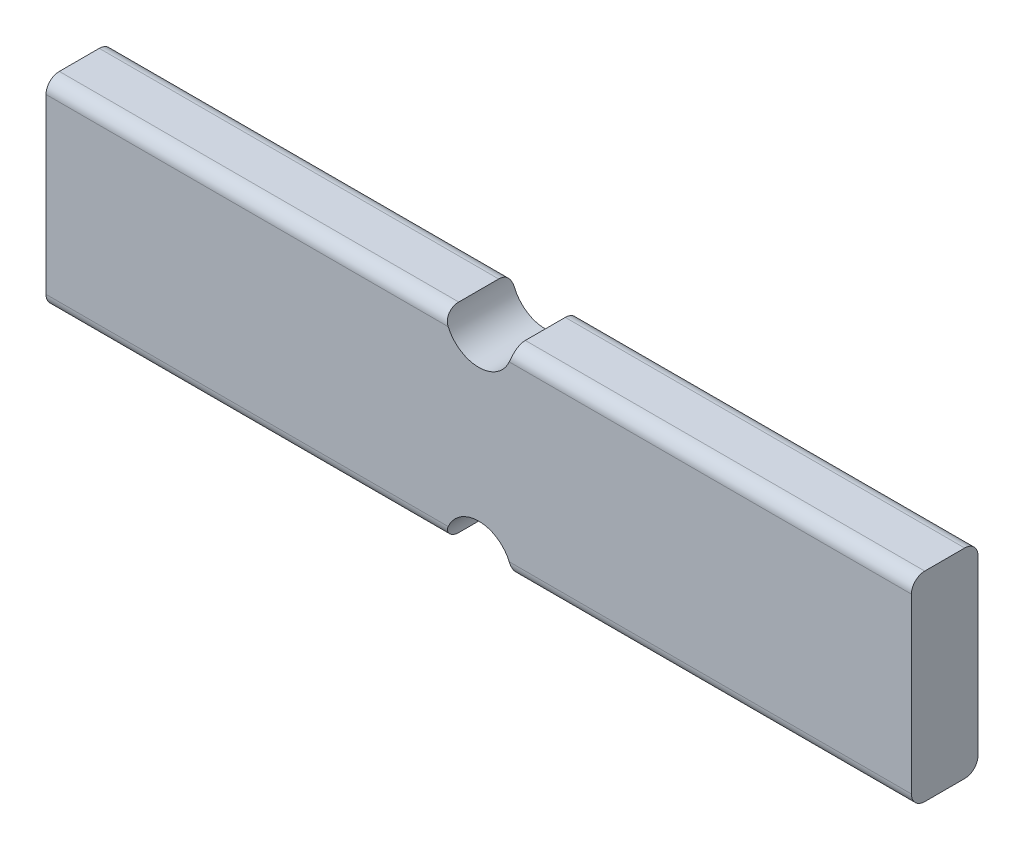
SolidWorks part; units mm, degrees
ref_plane "Front Plane" through (0, 0, 0) normal (0, 0, 1) x (1, 0, 0)
ref_plane "Top Plane" through (0, 0, 0) normal (0, 1, 0) x (1, 0, 0)
ref_plane "Right Plane" through (0, 0, 0) normal (1, 0, 0) x (0, 0, -1)
sketch "Sketch1" plane through (0, 0, 0) normal (0, 0, 1) x (1, 0, 0)
  line L0 (82.55, 74.4922) -> (82.55, -31.3198) construction
  line L1 (0, 0) -> (76.2, 0)
  line L2 (0, 0) -> (0, 38.1)
  line L3 (0, 38.1) -> (76.2, 38.1)
  line L4 (165.1, 0) -> (165.1, 38.1)
  line L5 (88.9, 38.1) -> (165.1, 38.1)
  line L6 (88.9, 0) -> (165.1, 0)
  arc A0 (88.9, 0) -> (76.2, 0) centre (82.55, 0) ccw
  arc A1 (76.2, 38.1) -> (88.9, 38.1) centre (82.55, 38.1) ccw
  dimension "D3" = 82.55
  dimension "D4" = 6.35
  dimension "D5" = 6.35
  dimension "D1" = 165.1
  dimension "D2" = 38.1
  dimension "D6" = 38.1
extrude "Extrude1" add sketch "Sketch1" along normal blind 12.7
ref_axis "Axis1" through (82.55, 38.1, 12.7) along (0, 0, -1)
fillet "Fillet1" radius 2.54 8 edges at (127, 0, 0) (38.1, 0, 0) (127, 0, 12.7) (38.1, 0, 12.7) (127, 38.1, 12.7) (127, 38.1, 0) (38.1, 38.1, 0) (38.1, 38.1, 12.7)
